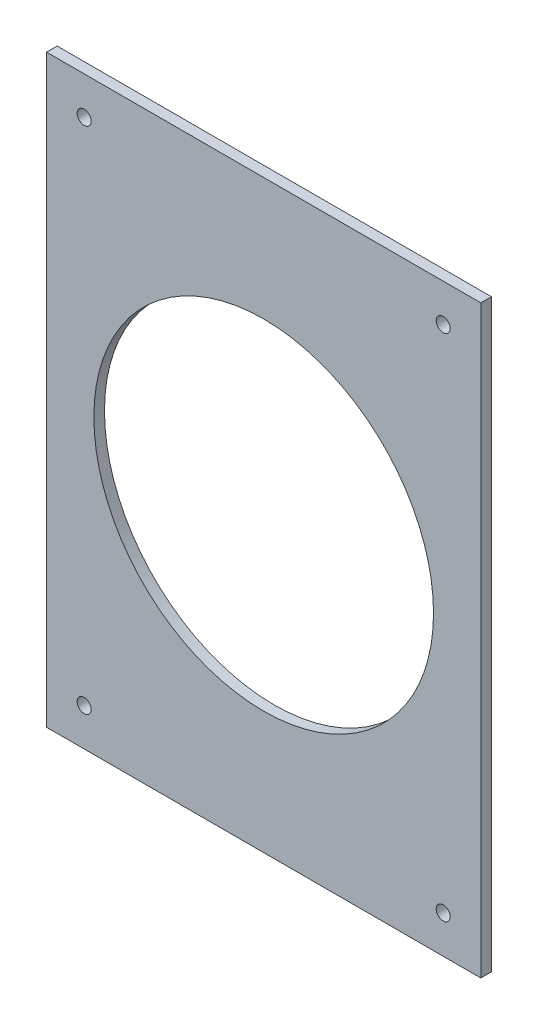
SolidWorks part; units mm, degrees
ref_plane "Front Plane" through (0, 0, 0) normal (0, 0, 1) x (1, 0, 0)
ref_plane "Top Plane" through (0, 0, 0) normal (0, 1, 0) x (1, 0, 0)
ref_plane "Right Plane" through (0, 0, 0) normal (1, 0, 0) x (0, 0, -1)
sketch "Sketch1" plane through (0, 0, 0) normal (0, 0, 1) x (1, 0, 0)
  line L0 (0, 0) -> (-259.8, 0)
  line L1 (-259.8, 0) -> (-259.8, 349.8)
  line L2 (-259.8, 349.8) -> (0, 349.8)
  line L3 (0, 349.8) -> (0, 0)
  line L4 (-129.9, 174.9) -> (-129.9, 0) construction
  line L5 (-129.9, 174.9) -> (-259.8, 174.9) construction
  line L6 (45, -32.1442) -> (0, -32.1442) construction
  line L7 (0, -32.1442) -> (0, 0) construction
  line L8 (0, -32.1442) -> (-259.8, -32.1442) construction
  line L9 (-259.8, -32.1442) -> (-304.8, -32.1442) construction
  line L10 (0, 0) -> (45, 0) construction
  line L11 (45, 0) -> (45, 45) construction
  line L12 (45, 45) -> (45, 304.8) construction
  line L13 (45, 304.8) -> (45, 349.8) construction
  line L14 (45, 349.8) -> (0, 349.8) construction
  line L15 (-259.8, -32.1442) -> (-259.8, 0) construction
  circle A0 centre (-129.9, 174.9) radius 101.6
  point P11 (39.358, 38.0163)
  point P16 (45, 22.5)
  point P19 (45, 327.3)
  point P20 (-282.3, -32.1442)
  point P21 (22.5, -32.1442)
  dimension "D2" = 203.2
  dimension "D1" = 304.8
  dimension "D3" = 304.8
  dimension "D4" = 45
  dimension "D5" = 45
  dimension "D6" = 45
  dimension "D7" = 45
extrude "Boss-Extrude1" add sketch "Sketch1" along normal blind 6.35
hole_wizard "M8 Clearance Hole1" positions "Sketch2" profile "Sketch3" hole size "M8" standard "ANSI Metric"
sketch "Sketch2" plane through (0, 0, 6.35) normal (0, 0, 1) x (1, 0, 0)
  line L0 (-237.3, 327.3) -> (-237.3, 22.5) construction
  line L1 (-237.3, 22.5) -> (-22.5, 22.5) construction
  line L2 (-22.5, 22.5) -> (-22.5, 327.3) construction
  line L3 (-22.5, 327.3) -> (-237.3, 327.3) construction
  line L5 (-129.9, 327.3) -> (-129.9, 349.8) construction
  line L6 (0, 349.8) -> (-259.8, 349.8) construction
  line L8 (-237.3, 174.9) -> (-259.8, 174.9) construction
  line L9 (-259.8, 349.8) -> (-259.8, 0) construction
  point P0 (-237.3, 327.3)
  point P2 (-22.5, 327.3)
  point P4 (-22.5, 22.5)
  point P6 (-237.3, 22.5)
  dimension "D1" = 22.5
  dimension "D2" = 22.5
sketch "Sketch3" plane through (-237.3, 327.3, 6.35) normal (1, 0, 0) x (0, -1, 0)
  line L0 (0, 0) -> (0, 78.7236)
  line L1 (0, 78.7236) -> (4.2, 76.2)
  line L2 (4.2, 76.2) -> (4.2, 0)
  line L5 (4.2, 0) -> (0, 0)
  line L10 (0, 78.7236) -> (-4.2, 76.2) construction
  line L11 (0, -6.35) -> (0, 107.95) construction
  dimension "Hole Dia." = 8.4
  dimension "Hole Depth" = 76.2
  dimension "Drill Angle" = 118
ref_axis "Axis1" through (0, 0, 0) along (0, 1, 0)
ref_axis "Axis2" through (-259.8, 0, 0) along (1, 0, 0)
ref_axis "Axis3" through (0, 0, 6.35) along (0, 0, -1)
